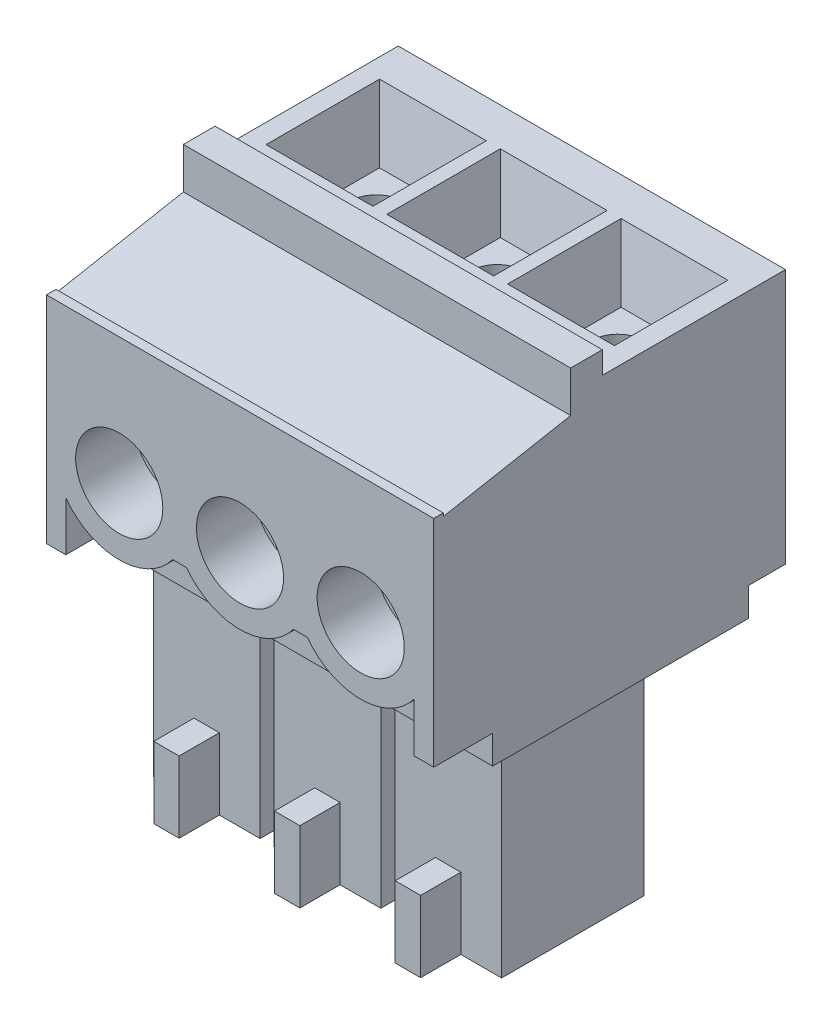
SolidWorks part; units mm, degrees
material "PTFE (general)"
ref_plane "Front Plane" through (0, 0, 0) normal (0, 0, 1) x (1, 0, 0)
ref_plane "Top Plane" through (0, 0, 0) normal (0, 1, 0) x (1, 0, 0)
ref_plane "Right Plane" through (0, 0, 0) normal (1, 0, 0) x (0, 0, -1)
sketch "Sketch1" plane through (0, 0, 0) normal (0, 1, 0) x (1, 0, 0)
  line L1 (6.11, -5.55) -> (-6.11, -5.55)
  line L2 (6.11, -5.55) -> (6.11, 5.55)
  line L3 (6.11, 5.55) -> (-6.11, 5.55)
  line L4 (-6.11, -5.55) -> (-6.11, 5.55)
  line L5 (6.11, -5.55) -> (-6.11, 5.55) construction
  line L6 (6.11, 5.55) -> (-6.11, -5.55) construction
  point P0 (0, 0)
  dimension "DimB" = 12.22
  dimension "D2" = 11.1
extrude "Boss-Extrude1" add sketch "Sketch1" along normal blind 9.65
sketch "Sketch2" plane through (6.11, 0, 0) normal (1, 0, 0) x (0, 0, -1)
  line L0 (-1.23, 9.65) -> (-1.23, 8.35)
  line L1 (-5.55, 9.65) -> (5.55, 9.65) construction
  line L2 (-1.23, 8.35) -> (-5.25, 7.6)
  line L3 (-1.23, 9.65) -> (-5.55, 9.65)
  line L4 (-5.55, 9.65) -> (-5.55, 0) construction
  line L5 (-5.55, 7.7) -> (-5.25, 7.7)
  line L6 (-5.25, 7.7) -> (-5.25, 7.6)
  line L7 (-5.55, 7.7) -> (-5.55, 9.65)
  line L8 (-5.55, 0) -> (5.55, 0) construction
  line L10 (5.55, 9.65) -> (-0.23, 9.65)
  line L11 (5.55, 9.65) -> (5.55, 8.95)
  line L12 (5.55, 8.95) -> (-0.23, 8.95)
  line L13 (-0.23, 9.65) -> (-0.23, 8.95)
  dimension "D1" = 6.78
  dimension "D2" = 0.3
  dimension "D3" = 7.7
  dimension "D4" = 0.1
  dimension "D5" = 1.3
  dimension "D6" = 1
  dimension "D7" = 0.7
extrude "Cut-Extrude1" cut sketch "Sketch2" against normal through all
sketch "Sketch4" plane through (6.11, 0, 0) normal (1, 0, 0) x (0, 0, -1)
  line L0 (5.55, 8.95) -> (5.55, 0) construction
  line L1 (-5.55, 0) -> (-3.69, 0)
  line L2 (-5.55, 0) -> (-5.55, 0.9)
  line L3 (-5.55, 0.9) -> (-3.69, 0.9)
  line L4 (-3.69, 0) -> (-3.69, 0.9)
  line L5 (5.55, 0) -> (4.39, 0)
  line L6 (5.55, 0) -> (5.55, 0.9)
  line L7 (5.55, 0.9) -> (4.39, 0.9)
  line L8 (4.39, 0) -> (4.39, 0.9)
  dimension "D1" = 0.9
  dimension "D2" = 1.86
  dimension "D3" = 1.16
extrude "Cut-Extrude3" cut sketch "Sketch4" against normal through all
sketch "Sketch5" plane through (0, 0, 0) normal (0, -1, 0) x (1, 0, 0)
  line L1 (-5.49, 2.79) -> (5.49, 2.79)
  line L2 (-5.49, 2.79) -> (-5.49, -4.39)
  line L3 (-5.49, -4.39) -> (5.49, -4.39)
  line L4 (5.49, 2.79) -> (5.49, -4.39)
  line L5 (-6.11, -4.39) -> (6.11, -4.39) construction
  line L6 (-6.11, -4.39) -> (-6.11, 3.69) construction
  line L7 (6.11, 3.69) -> (6.11, -4.39) construction
  line L8 (-6.11, 3.69) -> (6.11, 3.69) construction
  dimension "D1" = 0.62
  dimension "D2" = 0.62
  dimension "D3" = 0.9
extrude "Cut-Extrude4" cut sketch "Sketch5" against normal up to surface (0.9 mm away) up to face at (0, 0.9, -4.97)
sketch "Sketch6" plane through (0, 0.9, 0) normal (0, -1, 0) x (1, 0, 0)
  line L0 (5.49, -4.39) -> (6.11, -4.39) construction
  line L1 (5.49, 2.79) -> (2.12, 2.79)
  line L2 (5.49, 2.79) -> (5.49, -4.39)
  line L3 (5.49, -4.39) -> (2.12, -4.39)
  line L4 (2.12, 2.79) -> (2.12, -4.39)
  line L5 (5.49, -4.39) -> (5.49, 2.79) construction
  line L7 (-6.11, 3.69) -> (6.11, 3.69) construction
  point P9 (0, 3.69)
  dimension "D1" = 3.37
  dimension "D2" = 0.9
extrude "Boss-Extrude2" add sketch "Sketch6" along normal offset from surface (7.45 mm away) 15.5 up to face at (0, 8.95, -2.66)
sketch "Sketch7" plane through (0, -6.55, 0) normal (0, -1, 0) x (1, 0, 0)
  line L0 (3.805, -4.39) -> (3.805, 2.79) construction
  line L1 (2.12, -4.39) -> (5.49, -4.39) construction
  line L2 (5.49, 2.79) -> (2.12, 2.79) construction
  line L4 (3.405, 4.06) -> (4.205, 4.06)
  line L5 (3.405, 4.06) -> (3.405, 2.79)
  line L6 (3.405, 2.79) -> (4.205, 2.79)
  line L7 (4.205, 4.06) -> (4.205, 2.79)
  line L8 (3.405, 4.06) -> (4.205, 2.79) construction
  line L9 (3.405, 2.79) -> (4.205, 4.06) construction
  point P6 (3.805, 3.425)
  dimension "D1" = 1.27
  dimension "D2" = 0.8
extrude "Boss-Extrude3" add sketch "Sketch7" against normal blind 2.25
sketch "Sketch8" plane through (0, -6.55, 0) normal (0, -1, 0) x (1, 0, 0)
  line L0 (2.12, -1.7) -> (2.905, -1.7)
  line L1 (2.12, 2.79) -> (2.12, -4.39) construction
  line L2 (5.49, -1.7) -> (4.705, -1.7)
  line L3 (5.49, -4.39) -> (5.49, 2.79) construction
  line L4 (2.12, -1.7) -> (2.12, -4.39)
  line L5 (2.12, -4.39) -> (5.49, -4.39)
  line L6 (5.49, -4.39) -> (5.49, -1.7)
  line L7 (3.805, -1.34) -> (3.805, 4.06) construction
  line L8 (4.205, 4.06) -> (3.405, 4.06) construction
  line L9 (2.12, -1.7) -> (2.12, 2.79) construction
  line L10 (2.12, 0.545) -> (5.49, 0.545) construction
  line L11 (3.405, 2.79) -> (2.12, 2.79) construction
  line L12 (4.23, 0.12) -> (3.38, 0.12) construction
  line L13 (4.23, 0.12) -> (4.23, 0.97) construction
  line L14 (4.23, 0.97) -> (3.38, 0.97) construction
  line L15 (3.38, 0.12) -> (3.38, 0.97) construction
  line L16 (4.23, 0.12) -> (3.38, 0.97) construction
  line L17 (4.23, 0.97) -> (3.38, 0.12) construction
  arc A0 (2.905, -1.7) -> (4.705, -1.7) centre (3.805, -2.645) cw
  circle A1 centre (3.805, 0.545) radius 0.601
  point P17 (3.805, 4.06)
  point P22 (3.805, 0.545)
  dimension "D1" = 0.36
  dimension "D2" = 1.8
  dimension "D3" = 5.76
  dimension "D4" = 0.85
extrude "Cut-Extrude5" cut sketch "Sketch8" against normal up to surface (6.55 mm away) up to face at (0.2356, 0, -0.2011)
fillet "Fillet1" radius 0.2 1 edges at (3.805, -6.55, -0.056)
sketch "Sketch9" plane through (0, 0, 5.55) normal (0, 0, 1) x (1, 0, 0)
  line L0 (2.12, 2.4551) -> (2.12, 0.9)
  line L1 (2.12, 0.9) -> (5.49, 0.9)
  line L2 (5.49, 0.9) -> (5.49, 2.4551)
  line L3 (3.805, 1.605) -> (3.805, 0.9) construction
  line L4 (5.49, -6.55) -> (5.49, 0) construction
  line L5 (2.12, -6.55) -> (2.12, 0) construction
  line L6 (-6.11, 0.9) -> (6.11, 0.9) construction
  line L7 (-6.11, 7.7) -> (6.11, 7.7) construction
  arc A0 (2.12, 2.4551) -> (5.49, 2.4551) centre (3.805, 3.7) ccw
  circle A1 centre (3.805, 3.7) radius 1.375
  dimension "D1" = 0.72
  dimension "D3" = 2.75
  dimension "D2" = 4
extrude "Cut-Extrude6" cut sketch "Sketch9" against normal up to surface (1.86 mm away) up to face at (0, 0.45, 3.69)
sketch "Sketch11" plane through (0, 8.95, 0) normal (0, 1, 0) x (1, 0, 0)
  line L0 (5.49, 1.7) -> (5.49, -2.79) construction
  line L1 (5.49, 0.77) -> (2.12, 0.77)
  line L2 (5.49, 0.77) -> (5.49, 4.35)
  line L3 (5.49, 4.35) -> (2.12, 4.35)
  line L4 (2.12, 0.77) -> (2.12, 4.35)
  line L5 (2.12, -2.79) -> (2.12, 1.7) construction
  line L6 (-6.11, 5.55) -> (6.11, 5.55) construction
  line L7 (-6.11, -0.23) -> (6.11, -0.23) construction
  dimension "D1" = 1.2
  dimension "D2" = 1
extrude "Cut-Extrude8" cut sketch "Sketch11" against normal blind 2 draft 12
sketch "Sketch12" plane through (0, 6.95, 0) normal (0, 1, 0) x (1, 0, 0)
  line L0 (2.5451, 3.9249) -> (2.5451, 1.1951) construction
  line L1 (2.5451, 1.1951) -> (5.0649, 1.1951) construction
  circle A0 centre (3.805, 2.56) radius 0.815
  point P4 (2.5451, 2.56)
  point P7 (3.805, 1.1951)
  dimension "D1" = 1.63
extrude "Cut-Extrude9" cut sketch "Sketch12" against normal offset from surface (4.8 mm away) 6.8 up to face at (3.805, 8.95, -2.56)
pattern_linear "LPattern1" count 3 spacing 3.81 along (-1, 0, 0) of "Boss-Extrude2", "Boss-Extrude3", "Cut-Extrude5", "Fillet1", "Cut-Extrude6", "Cut-Extrude8", "Cut-Extrude9"
sketch "Sketch10" plane through (0, 0, 5.55) normal (0, 0, 1) x (1, 0, 0)
  line L1 (1.68, 0.9) -> (2.12, 0.9)
  line L2 (1.68, 0.9) -> (1.68, 2.4551)
  line L3 (1.68, 2.4551) -> (2.12, 2.4551)
  line L4 (2.12, 0.9) -> (2.12, 2.4551)
extrude "Cut-Extrude7" cut sketch "Sketch10" against normal up to surface (1.86 mm away) up to face at (-0.0037, 1.2113, 3.69)
pattern_linear "LPattern2" count 2 spacing 3.81 along (1, 0, 0) of "Cut-Extrude7"
other "CPoint1" parameters "Diameter"=2.0523, "StubLength"=2
ref_axis "Axis1" through (3.805, 16.95, -2.56) along (0, -1, 0)
other "CPoint2" parameters "Diameter"=2.0523, "StubLength"=2
ref_axis "Axis2" through (-0.005, 16.95, -2.56) along (0, -1, 0)
other "CPoint3"
ref_axis "Axis3" through (-3.815, 16.95, -2.56) along (0, -1, 0)
other "CPoint4"
ref_axis "Axis4" through (9.52, 16.95, -2.56) along (0, -1, 0)
other "CPoint5"
ref_axis "Axis5" through (5.71, 16.95, -2.56) along (0, -1, 0)
other "CPoint6"
ref_axis "Axis6" through (1.9, 16.95, -2.56) along (0, -1, 0)
other "CPoint7"
ref_axis "Axis7" through (-1.91, 16.95, -2.56) along (0, -1, 0)
other "CPoint8"
ref_axis "Axis8" through (-5.72, 16.95, -2.56) along (0, -1, 0)
other "CPoint9"
ref_axis "Axis9" through (-9.53, 16.95, -2.56) along (0, -1, 0)
other "CPoint10"
ref_axis "Axis10" through (-13.34, 16.95, -2.56) along (0, -1, 0)
other "CPoint11"
ref_axis "Axis11" through (-17.15, 16.95, -2.56) along (0, -1, 0)
other "CPoint12"
ref_axis "Axis12" through (-20.96, 16.95, -2.56) along (0, -1, 0)
